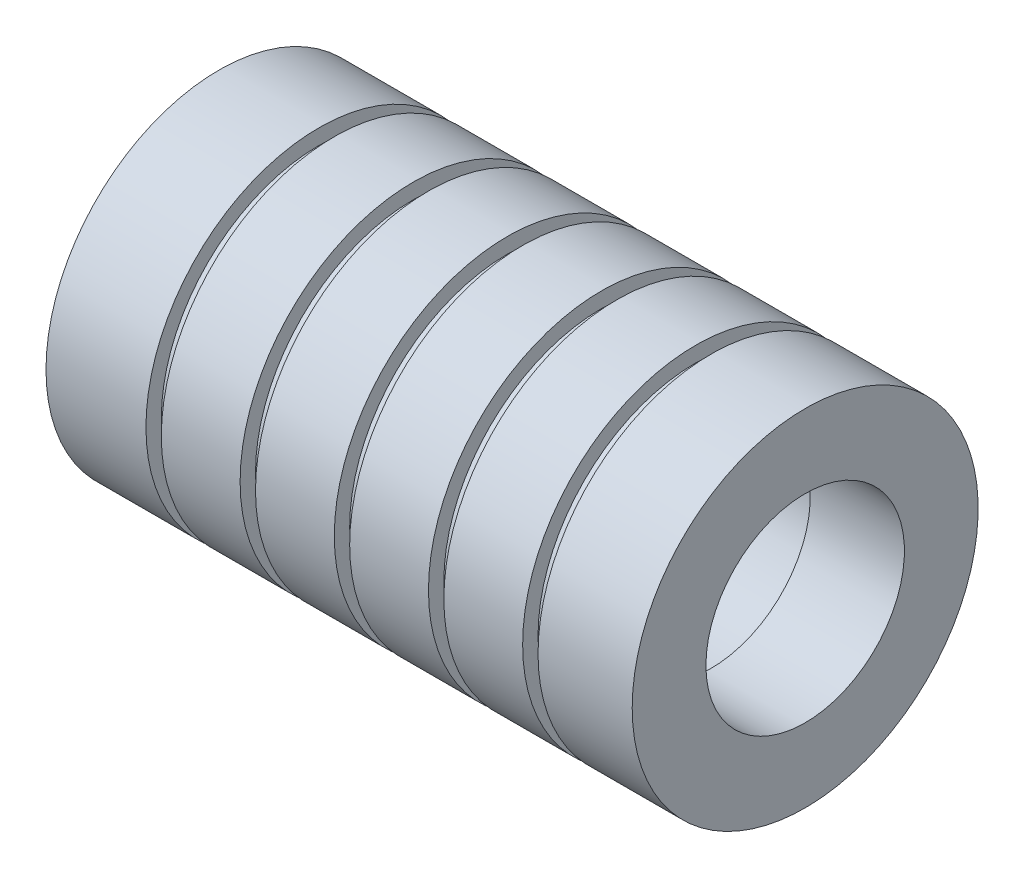
SolidWorks part; units mm, degrees
ref_plane "Front Plane" through (0, 0, 0) normal (0, 0, 1) x (1, 0, 0)
ref_plane "Top Plane" through (0, 0, 0) normal (0, 1, 0) x (1, 0, 0)
ref_plane "Right Plane" through (0, 0, 0) normal (1, 0, 0) x (0, 0, -1)
sketch "Sketch1" plane through (0, 0, 0) normal (0, 0, 1) x (1, 0, 0)
  line L0 (0, 0) -> (36.5459, 0) construction
  line L1 (-7.62, 9.0988) -> (-7.62, 11.43)
  line L3 (31.115, 11.43) -> (31.115, 6.5588)
  line L4 (31.115, 6.5588) -> (24.892, 6.5588)
  line L5 (24.892, 6.5588) -> (24.892, 7.0668)
  line L6 (24.892, 7.0668) -> (18.669, 7.0668)
  line L7 (18.669, 7.0668) -> (18.669, 7.5748)
  line L8 (18.669, 7.5748) -> (12.446, 7.5748)
  line L9 (12.446, 7.5748) -> (12.446, 8.0828)
  line L10 (12.446, 8.0828) -> (6.223, 8.0828)
  line L11 (6.223, 8.0828) -> (6.223, 8.5908)
  line L12 (6.223, 8.5908) -> (0, 8.5908)
  line L13 (0, 8.5908) -> (0, 9.0988)
  line L14 (0, 9.0988) -> (-7.62, 9.0988)
  line L15 (-7.62, 11.43) -> (-1.016, 11.43)
  line L16 (-1.016, 11.43) -> (-1.016, 10.414)
  line L17 (-1.016, 10.414) -> (0, 10.414)
  line L18 (0, 10.414) -> (0, 11.43)
  line L19 (0, 11.43) -> (5.207, 11.43)
  line L20 (5.207, 11.43) -> (5.207, 10.414)
  line L21 (5.207, 10.414) -> (6.223, 10.414)
  line L22 (6.223, 10.414) -> (6.223, 11.43)
  line L23 (6.223, 11.43) -> (11.43, 11.43)
  line L24 (11.43, 11.43) -> (11.43, 10.414)
  line L25 (11.43, 10.414) -> (12.446, 10.414)
  line L26 (12.446, 10.414) -> (12.446, 11.43)
  line L27 (12.446, 11.43) -> (17.653, 11.43)
  line L28 (17.653, 11.43) -> (17.653, 10.414)
  line L29 (17.653, 10.414) -> (18.669, 10.414)
  line L30 (18.669, 10.414) -> (18.669, 11.43)
  line L31 (18.669, 11.43) -> (23.876, 11.43)
  line L32 (23.876, 11.43) -> (23.876, 10.414)
  line L33 (23.876, 10.414) -> (24.892, 10.414)
  line L34 (24.892, 10.414) -> (24.892, 11.43)
  line L35 (24.892, 11.43) -> (31.115, 11.43)
  dimension "D1" = 6.5588
  dimension "D2" = 0.508
  dimension "D4" = 11.43
  dimension "D5" = 1.016
  dimension "D6" = 1.016
  dimension "D8" = 1.016
  dimension "D9" = 1.016
  dimension "D10" = 1.016
  dimension "D11" = 1.016
  dimension "D3" = 6.223
  dimension "D7" = 7.62
revolve "Revolve1" add sketch "Sketch1" angle 360 about L0
ref_plane "Plane1" through (-0.508, 0, 0) normal (-1, 0, 0) x (0, 0, 1)
ref_plane "Plane2" through (5.715, 0, 0) normal (-1, 0, 0) x (0, 0, 1)
ref_plane "Plane3" through (11.938, 0, 0) normal (1, 0, 0) x (0, 0, -1)
ref_plane "Plane4" through (18.161, 0, 0) normal (-1, 0, 0) x (0, 0, 1)
ref_plane "Plane5" through (24.384, 0, 0) normal (1, 0, 0) x (0, 0, -1)
ref_plane "Plane6" through (0, 11.43, 0) normal (0, 1, 0) x (1, 0, 0)
ref_axis "Axis1" through (0, 0, 0) along (-1, 0, 0)
sketch "Sketch4" plane through (-0.508, 0, 0) normal (-1, 0, 0) x (0, 0, 1)
  point P0 (0, 0)
sketch "Sketch5" plane through (5.715, 0, 0) normal (-1, 0, 0) x (0, 0, 1)
  point P0 (0, 0)
sketch "Sketch6" plane through (11.938, 0, 0) normal (1, 0, 0) x (0, 0, -1)
  point P0 (0, 0)
sketch "Sketch7" plane through (18.161, 0, 0) normal (-1, 0, 0) x (0, 0, 1)
  point P0 (0, 0)
sketch "Sketch8" plane through (24.384, 0, 0) normal (1, 0, 0) x (0, 0, -1)
  point P0 (0, 0)
sketch "Sketch9" plane through (0, 11.43, 0) normal (0, 1, 0) x (1, 0, 0)
  point P0 (24.384, 0)
  point P2 (18.161, 0)
  point P4 (11.938, 0)
  point P6 (5.715, 0)
  point P10 (0, 0)
  point P11 (-0.508, 0)
hole_wizard "#65 (0.035) Diameter Hole1" positions "Sketch9" profile "Sketch10" hole size "#65" standard "ANSI Inch" end condition up to next
sketch "Sketch10" plane through (24.384, 11.43, 0) normal (1, 0, 0) x (0, 0, 1)
  line L0 (0, 0) -> (0, 4.3632)
  line L1 (0, 4.3632) -> (0.4445, 4.3632)
  line L2 (0.4445, 4.3632) -> (0.4445, 0)
  line L5 (0.4445, 0) -> (0, 0)
  line L11 (0, -6.35) -> (0, 107.95) construction
  dimension "Thru Hole Dia." = 0.889
  dimension "Thru Hole Depth" = 4.3632
equation "\"dia1\"= .47in"
equation "\"kero_radius\"=0.334in"
equation "\"lox_radius\"=0.23622in"
equation "\"Cavity_width\"=0.031in"
equation "\"tooth_width\"=0.01in"
equation "\"cavity_depth\"=0.031in"
equation "\"seal_step\"=0.02in"
equation "\"purge_length\"=0.04in"
equation "\"D1@Sketch1\"=\"lox_radius\"+\"seal_step\"+\"radial_clearance\""
equation "\"D2@Sketch1\"=\"seal_step\""
equation "\"insert_radius\" = 0.55in"
equation "\"recycle_groove width\" = 0.04in"
equation "\"D5@Sketch1\"=\"recycle_groove width\""
equation "\"recycle_groove_depth\" = 0.04in"
equation "\"D6@Sketch1\"=\"recycle_groove_depth\""
equation "\"N2_purge_width\"= .04in"
equation "\"N2_purge_depth\"= .04in"
equation "\"drain_width\"= .04in"
equation "\"drain_depth\"= .04in"
equation "\"D9@Sketch1\"=\"drain_depth\""
equation "\"D8@Sketch1\"=\"drain_width\""
equation "\"D10@Sketch1\"=\"N2_purge_depth\""
equation "\"D11@Sketch1\"=\"N2_purge_width\""
equation "\"radial_clearance\"= .002in"
equation "\"D3@Sketch1\"=\"tooth_width\"*5+\"Cavity_width\"*5+\"purge_length\""
